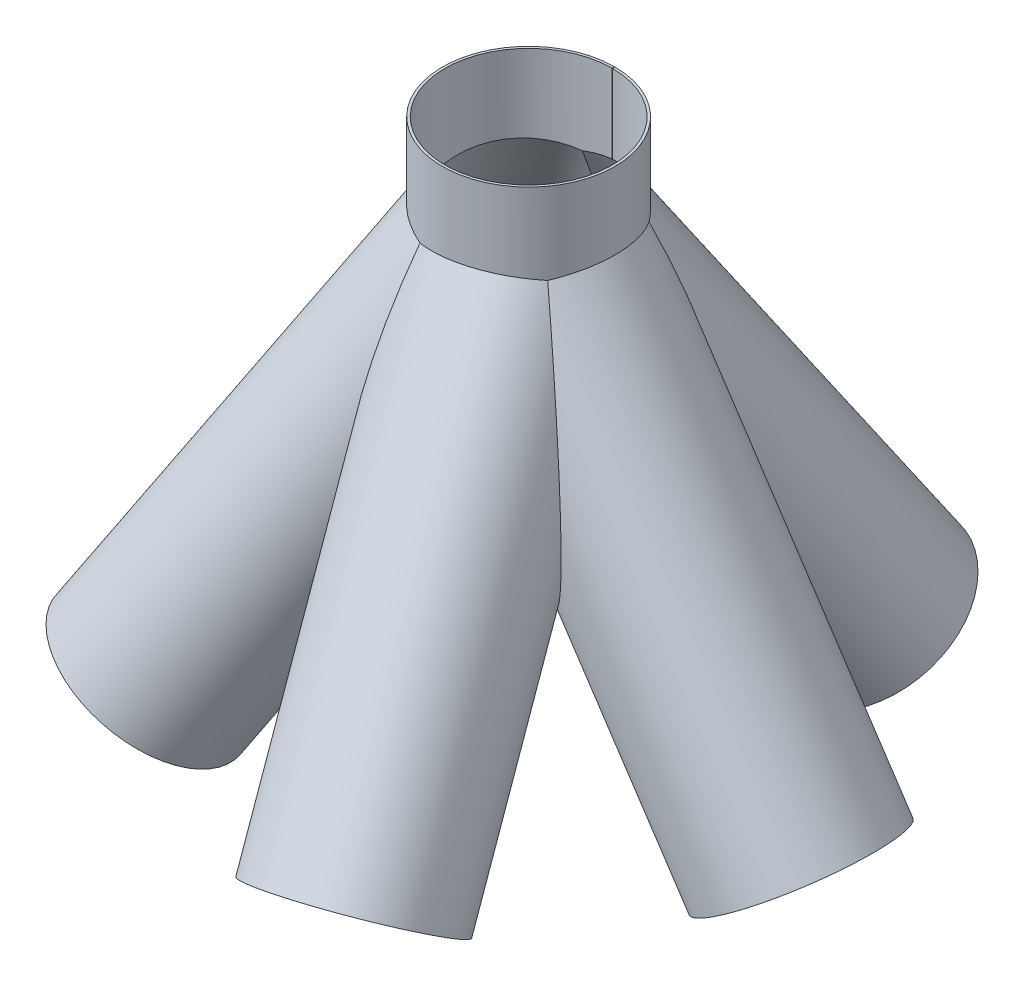
SolidWorks part; units mm, degrees
ref_plane "前视基准面" through (0, 0, 0) normal (0, 0, 1) x (1, 0, 0)
ref_plane "上视基准面" through (0, 0, 0) normal (0, 1, 0) x (1, 0, 0)
ref_plane "右视基准面" through (0, 0, 0) normal (1, 0, 0) x (0, 0, -1)
sketch "草图1" plane through (0, 0, 0) normal (0, 0, 1) x (1, 0, 0)
  line L0 (0, 250) -> (0, 0) construction
  line L1 (0, 0) -> (663.325, -1000) construction
  line L2 (0, 0) -> (0, -1116.0819) construction
  line L3 (-210, 250) -> (210, 250) construction
  line L4 (-210, 0) -> (210, 0) construction
  line L5 (-210, -63.3174) -> (210, 63.3174) construction
  line L6 (210, 250) -> (210, 63.3174) construction
  line L7 (210, 63.3174) -> (838.325, -883.9181) construction
  line L8 (838.325, -883.9181) -> (488.325, -1116.0819) construction
  line L9 (0, -1116.0819) -> (0, -1122.0819) construction
  line L10 (0, -1116.0819) -> (0, 250)
  dimension "h" = 250
  dimension "d" = 420
  dimension "t" = 6
  dimension "c" = 1200
  dimension "hm" = 1000
sketch "草图2" plane through (0, 0, 0) normal (0, 1, 0) x (1, 0, 0)
  line L0 (0, 210) -> (0, -210) construction
  line L1 (0, 0) -> (169.8936, 123.4349) construction
  line L2 (0, 0) -> (169.8936, -123.4349) construction
  line L3 (0, 0) -> (210, 0) construction
  line L4 (0, 0) -> (663.325, 0) construction
  line L5 (0, 0) -> (-64.8936, 199.7219) construction
  line L6 (0, 0) -> (-64.8936, -199.7219) construction
  circle A0 centre (0, 0) radius 210
  dimension "D1" = 72
  dimension "D2" = 72
  dimension "D3" = 72
extrude "拉伸-薄壁1" add sketch "草图2" along normal up to vertex (250 mm away) thin up to point (0, 250, 0) thin type one direction reverse wall 6
ref_plane "基准面1" through (663.325, -1000, 0) normal (0.5528, -0.8333, 0) x (0.8333, 0.5528, 0)
ref_axis "基准轴1" through (0, 318.6041, 0) along (0, -1, 0)
sketch "草图3" plane through (663.325, -1000, 0) normal (0.5528, -0.8333, 0) x (0.8333, 0.5528, 0)
  circle A0 centre (0, 0) radius 210
extrude "拉伸-薄壁2" add sketch "草图3" against normal up to vertex (1200 mm away) separate body thin up to point (0, 0, 0) thin type one direction reverse wall 6
sketch "草图5" plane through (0, 0, 0) normal (0, 0, 1) x (1, 0, 0)
  line L0 (210, 63.3174) -> (-210, -63.3174)
extrude "切除-拉伸1" cut sketch "草图5" against normal through all and the other way through all
extrude "切除-拉伸2" cut sketch "草图5<2>" against normal through all and the other way through all flip side to cut
sketch "草图5<2>" plane through (0, 0, 0) normal (0, 0, 1) x (1, 0, 0) same geometry as "草图5"
ref_plane "基准面2" through (0, 0, 0) normal (-0.809, 0, -0.5878) x (-0.5878, 0, 0.809)
sketch "草图6" plane through (0, 0, 0) normal (-0.809, 0, -0.5878) x (-0.5878, 0, 0.809)
  line L0 (0, -1116.0819) -> (0, 250)
extrude "切除-拉伸3" cut sketch "草图6" against normal through all and the other way through all flip side to cut
ref_plane "基准面3" through (0, 0, 0) normal (0.809, 0, -0.5878) x (-0.5878, 0, -0.809)
sketch "草图7" plane through (0, 0, 0) normal (0.809, 0, -0.5878) x (-0.5878, 0, -0.809)
  line L0 (0, 250) -> (0, -1122.0819)
extrude "切除-拉伸4" cut sketch "草图7" against normal through all and the other way through all
ref_plane "基准面4" through (0, 0, 0) normal (-0.9511, 0, 0.309) x (0.309, 0, 0.9511)
sketch "草图8" plane through (0, 0, 0) normal (-0.9511, 0, 0.309) x (0.309, 0, 0.9511)
  line L0 (210, 63.3174) -> (-210, -63.3174)
extrude "切除-拉伸5" cut sketch "草图8" against normal through all and the other way through all
ref_plane "基准面5" through (0, 0, 0) normal (-0.5878, 0, -0.809) x (-0.809, 0, 0.5878)
sketch "草图9" plane through (0, 0, 0) normal (-0.5878, 0, -0.809) x (-0.809, 0, 0.5878)
  line L0 (210, 63.3174) -> (-210, -63.3174)
extrude "切除-拉伸6" cut sketch "草图9" against normal through all and the other way through all
ref_plane "基准面6" through (0, 0, 0) normal (0.5878, 0, -0.809) x (-0.809, 0, -0.5878)
sketch "草图10" plane through (0, 0, 0) normal (0.5878, 0, -0.809) x (-0.809, 0, -0.5878)
  line L0 (210, 63.3174) -> (-210, -63.3174)
extrude "切除-拉伸7" cut sketch "草图10" against normal through all and the other way through all
ref_plane "基准面7" through (0, 0, 0) normal (0.9511, 0, 0.309) x (0.309, 0, -0.9511)
sketch "草图11" plane through (0, 0, 0) normal (0.9511, 0, 0.309) x (0.309, 0, -0.9511)
  line L0 (210, 63.3174) -> (-210, -63.3174)
extrude "切除-拉伸8" cut sketch "草图11" against normal through all and the other way through all
extrude "切除-拉伸-薄壁3" cut sketch "草图1" against normal through all thin thin type mid plane wall 1
sketch "草图4" plane through (663.325, -1000, 0) normal (0.5528, -0.8333, 0) x (0.8333, 0.5528, 0)
  line L0 (0, 0) -> (-210, 0)
  circle A2 centre (0, 0) radius 210 construction
extrude "切除-拉伸-薄壁2" cut sketch "草图4" against normal through all thin thin type mid plane wall 1
pattern_circular "阵列(圆周)1" count 5 over 360 about axis through (0, 318.6041, 0) along (0, -1, 0) of bodies 112 104
equation "\"D5@拉伸-薄壁1\" = \"t@草图1\""
equation "\"D5@拉伸-薄壁2\" = \"t@草图1\""
